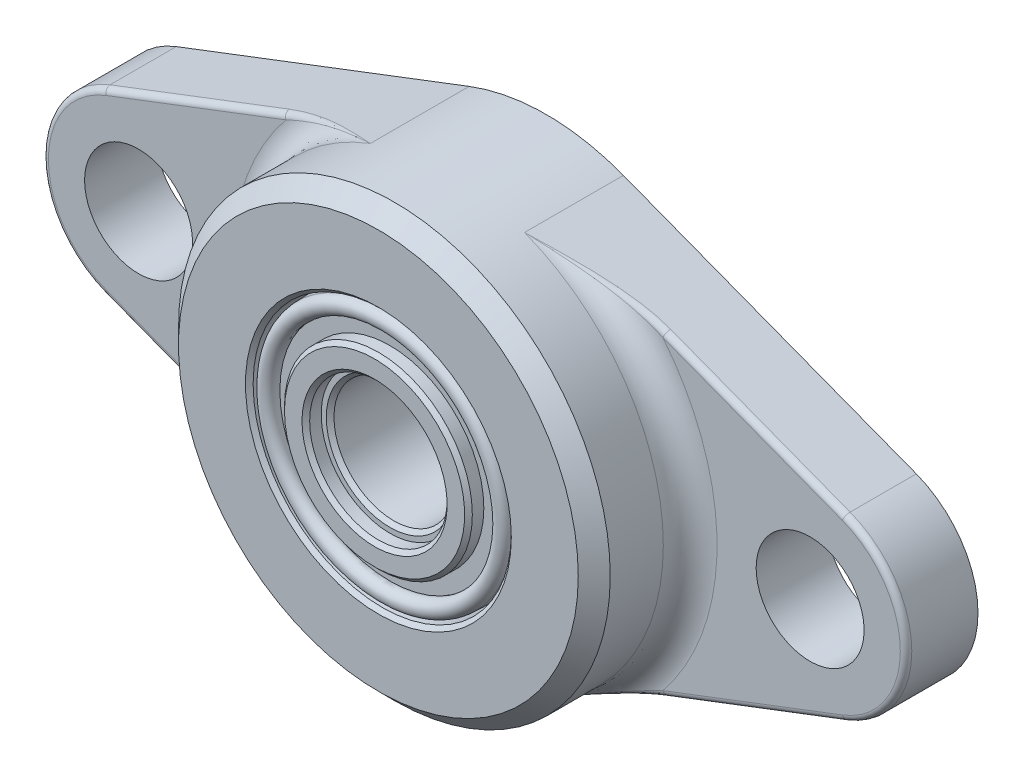
SolidWorks part; units mm, degrees
ref_plane "Front Plane" through (0, 0, 0) normal (0, 0, 1) x (1, 0, 0)
ref_plane "Top Plane" through (0, 0, 0) normal (0, 1, 0) x (1, 0, 0)
ref_plane "Right Plane" through (0, 0, 0) normal (1, 0, 0) x (0, 0, -1)
sketch "Sketch1" plane through (0, 0, 0) normal (0, 0, 1) x (1, 0, 0)
  line L0 (-22.225, 0) -> (22.225, 0) construction
  line L1 (0, 14.2875) -> (0, -14.2875) construction
  line L2 (-24.4929, 5.9312) -> (-5.1027, 13.3452)
  line L3 (5.1027, 13.3452) -> (24.4929, 5.9312)
  line L4 (24.4929, -5.9312) -> (5.1027, -13.3452)
  line L5 (-24.4929, -5.9312) -> (-5.1027, -13.3452)
  line L6 (-28.575, 0) -> (28.575, 0) construction
  line L7 (2.7973, 2.7973) -> (10.1028, 10.1028) construction
  circle A0 centre (-22.225, 0) radius 3.5719
  circle A1 centre (22.225, 0) radius 3.5719
  circle A2 centre (0, 0) radius 14.2875
  arc A3 (-24.4929, 5.9312) -> (-24.4929, -5.9312) centre (-22.225, 0) ccw
  arc A4 (24.4929, -5.9312) -> (24.4929, 5.9312) centre (22.225, 0) ccw
  circle A5 centre (0, 0) radius 3.956
  circle A6 centre (0, 0) radius 8.545 construction
  point P23 (6.0422, 6.0422)
  point P24 (0, 8.545)
  point P25 (0, 3.956)
  dimension "Mounting Hole" = 7.1437
  dimension "ID" = 7.9121
  dimension "D4" = 17.09
  dimension "Mounting Center" = 44.45
  dimension "Height" = 28.575
  dimension "Length" = 57.15
  dimension "D2" = 45
  dimension "D3" = 10.3315
  dimension "D1" = 4.5889
sketch "Sketch2" plane through (0, 0, 0) normal (1, 0, 0) x (0, 0, -1)
  line L0 (5.5562, 0) -> (-5.5562, 0) construction
  point P2 (0.7937, 0)
  point P4 (5.5562, 0)
  dimension "Width" = 11.1125
  dimension "flange thickness" = 4.7625
  dimension "Bearing Width" = 11.1125
sketch "Sketch3" plane through (0, 0, 0) normal (0, 0, 1) x (1, 0, 0)
  line L0 (-24.4929, 5.9312) -> (-5.1027, 13.3452) construction
  line L1 (5.1027, 13.3452) -> (24.4929, 5.9312) construction
  line L2 (24.4929, -5.9312) -> (5.1027, -13.3452) construction
  line L3 (-24.4929, -5.9312) -> (-5.1027, -13.3452) construction
  line L4 (-24.4929, 5.9312) -> (-5.1027, 13.3452)
  line L5 (5.1027, 13.3452) -> (24.4929, 5.9312)
  line L6 (24.4929, -5.9312) -> (5.1027, -13.3452)
  line L7 (-24.4929, -5.9312) -> (-5.1027, -13.3452)
  arc A0 (-24.4929, 5.9312) -> (-24.4929, -5.9312) centre (-22.225, 0) ccw construction
  circle A1 centre (-22.225, 0) radius 3.5719 construction
  circle A2 centre (0, 0) radius 14.2875 construction
  circle A3 centre (22.225, 0) radius 3.5719 construction
  arc A4 (24.4929, -5.9312) -> (24.4929, 5.9312) centre (22.225, 0) ccw construction
  arc A5 (-24.4929, 5.9312) -> (-24.4929, -5.9312) centre (-22.225, 0) ccw
  circle A6 centre (-22.225, 0) radius 3.5719
  arc A7 (-5.1027, -13.3452) -> (5.1027, -13.3452) centre (0, 0) ccw
  circle A8 centre (22.225, 0) radius 3.5719
  arc A9 (24.4929, -5.9312) -> (24.4929, 5.9312) centre (22.225, 0) ccw
  circle A10 centre (0, 0) radius 8.545 construction
  circle A11 centre (0, 0) radius 8.545
  arc A12 (5.1027, 13.3452) -> (-5.1027, 13.3452) centre (0, 0) ccw
extrude "Boss-Extrude1" add sketch "Sketch3" along normal up to vertex (-0.7937 mm away) from vertex at -5.5563 starting at point (0, 0, -5.5562)
sketch "Sketch4" plane through (0, 0, -0.7937) normal (0, 0, 1) x (1, 0, 0)
  circle A0 centre (0, 0) radius 14.2875 construction
  circle A1 centre (0, 0) radius 8.545 construction
  circle A2 centre (0, 0) radius 14.2875
  circle A3 centre (0, 0) radius 8.545
extrude "Boss-Extrude2" add sketch "Sketch4" along normal up to vertex
chamfer "Chamfer1" distance 0.254 angle 45 2 edges at (8.545, 0, 5.5562) (8.545, 0, -5.5562)
fillet "Fillet1" radius 1.778 2 edges
fillet "Fillet2" radius 0.381 10 edges at (8.643, 11.9916, -0.2459) (28.575, 0, -0.7937) (-8.643, 11.9916, -0.2459) (-28.575, 0, -0.7937) (-8.643, -11.9916, -0.2459) (8.643, -11.9916, -0.2459)
chamfer "Chamfer2" distance 1.0583 angle 45 1 edges at (14.2875, 0, 5.5562)
sketch "Sketch5" plane through (0, 0, 0) normal (1, 0, 0) x (0, 0, -1)
  line L0 (-5.5562, 3.956) -> (5.5563, 3.956)
  line L1 (-5.5562, 3.956) -> (-5.5562, 8.545)
  line L2 (-5.5562, 8.545) -> (5.5562, 8.545)
  line L3 (5.5562, 8.545) -> (5.5563, 3.956)
  line L4 (-5.5562, 0) -> (5.5562, 0) construction
  dimension "D1" = 11.1125
sketch "Sketch6" plane through (0, 0, 0) normal (1, 0, 0) x (0, 0, -1)
  line L0 (0, 8.545) -> (-5.0147, 8.3699)
  line L1 (-4.7942, 7.2852) -> (-4.7942, 6.2182)
  line L2 (-4.7942, 6.2182) -> (-5.8102, 6.2182)
  line L3 (-5.8102, 6.2182) -> (-5.8102, 4.5495)
  line L4 (-4.7942, 3.956) -> (-4.7942, 4.5495)
  line L5 (-4.7942, 4.5495) -> (-5.8102, 4.5495)
  line L6 (-5.5562, 3.956) -> (5.5563, 3.956) construction
  line L7 (-5.5562, 3.956) -> (-5.5562, 8.545) construction
  line L8 (-5.5562, 13.2292) -> (-5.5562, -13.2292) construction
  line L9 (-5.5562, 8.545) -> (5.5562, 8.545) construction
  line L10 (3.2702, 3.956) -> (3.2702, 4.5495)
  line L11 (3.2702, 4.5495) -> (4.2862, 4.5495)
  line L12 (4.2862, 4.5495) -> (4.2862, 6.2182)
  line L13 (4.2862, 6.2182) -> (1.7462, 6.2182)
  line L14 (1.7462, 6.2182) -> (1.7462, 7.2852)
  line L15 (1.7462, 7.2852) -> (5.5562, 7.2852)
  line L16 (5.5562, 8.545) -> (5.5562, 3.956) construction
  line L17 (5.5562, 7.2852) -> (5.5562, 8.545)
  line L18 (-4.7942, 3.956) -> (3.2702, 3.956)
  line L19 (0, 8.545) -> (5.5562, 8.545)
  line L20 (-5.5562, 0) -> (5.5562, 0) construction
  arc A0 (-5.0147, 8.3699) -> (-4.7942, 7.2852) centre (-4.9952, 7.8091) ccw
  dimension "D1" = 0.254
  dimension "D2" = 0.762
  dimension "D3" = 2
  dimension "D4" = 4.5889
  dimension "D5" = 1.6687
  dimension "D6" = 9.0989
  dimension "D7" = 1.0847
  dimension "D8" = 1.27
  dimension "D9" = 2.54
revolve "Revolve1" add sketch "Sketch6" angle 360 about L20
chamfer "Chamfer3" distance 0.254 angle 45 6 edges at (4.5495, 0, -4.2862) (6.2182, 0, -4.2862) (6.2182, 0, 5.8102) (4.5495, 0, 5.8102) (3.9561, 0, 4.7942) (3.9561, 0, -3.2702)
equation "\"D1@Chamfer2\"=(\"Width@Sketch2\"-\"flange thickness@Sketch2\")/6"
equation "\"D1@Sketch1\"=\"D3@Sketch1\"/2.25"
equation "\"D1@Sketch5\"=\"Bearing Width@Sketch2\""
equation "\"D5@Sketch6\"=\"D4@Sketch6\"/2.75"
equation "\"D6@Sketch6\"=\"ID@Sketch1\"*1.15"
equation "\"D7@Sketch6\"=\"D5@Sketch6\"*.65"
